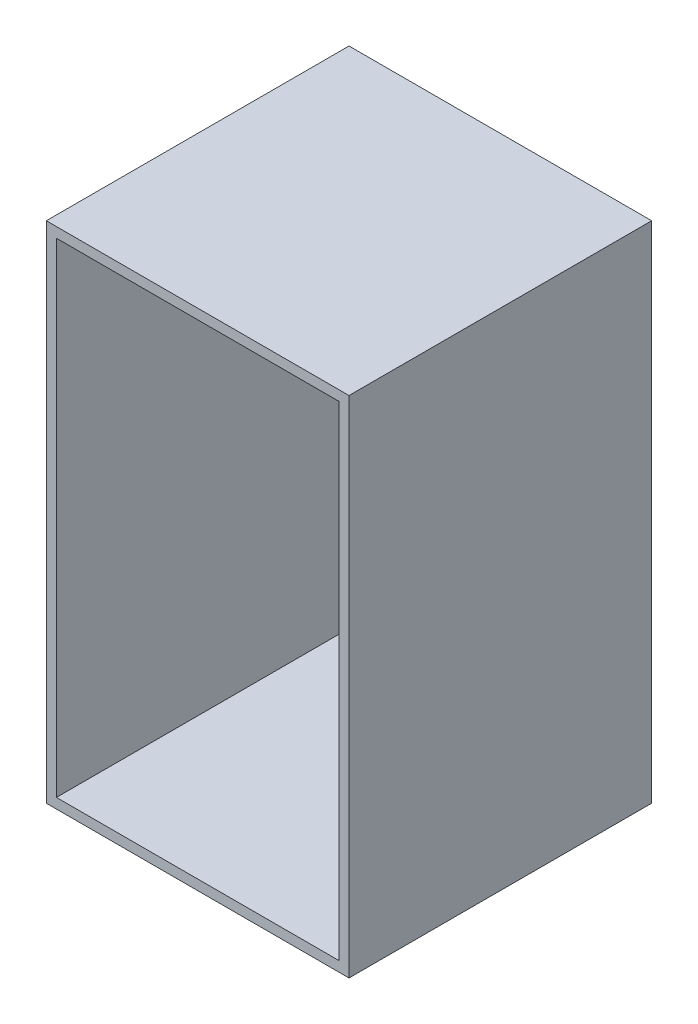
SolidWorks part; units mm, degrees
note: '?' marks a value the reader was unsure of.
ref_plane "Front Plane" through (0, 0, 0) normal (0, 0, 1) x (1, 0, 0)
ref_plane "Top Plane" through (0, 0, 0) normal (0, 1, 0) x (1, 0, 0)
ref_plane "Right Plane" through (0, 0, 0) normal (1, 0, 0) x (0, 0, -1)
sketch "Sketch1" plane through (0, 0, 0) normal (0, 1, 0) x (1, 0, 0)
  line L1 (-38.1, -38.1) -> (38.1, -38.1)
  line L2 (-38.1, -38.1) -> (-38.1, 38.1)
  line L3 (-38.1, 38.1) -> (38.1, 38.1)
  line L4 (38.1, -38.1) -> (38.1, 38.1)
  line L5 (-38.1, -38.1) -> (38.1, 38.1) construction
  line L6 (-38.1, 38.1) -> (38.1, -38.1) construction
  point P0 (0, 0)
  dimension "D1" = 76.2
  dimension "D2" = 76.2
extrude "box" add sketch "Sketch1" along normal blind 127
shell "hollow it" thickness 2.54
sketch "Sketch2" plane through (0, 0, -38.1) normal (0, 0, -1) x (-1, 0, 0)
  line L0 (-38.1, 127) -> (38.1, 127) construction
  line L1 (-29.21, 69.85) -> (-24.892, 69.85)
  line L2 (-29.21, 69.85) -> (-29.21, 6.35)
  line L3 (-29.21, 6.35) -> (-24.892, 6.35)
  line L4 (-24.892, 69.85) -> (-24.892, 6.35)
  line L6 (-38.1, 127) -> (-38.1, 0) construction
  dimension "D1" = 4.318
  dimension "D2" = 63.5
  dimension "D3" = 57.15
  dimension "D4" = 8.89
extrude "slider track" cut sketch "Sketch2" against normal up to surface (2.54 mm away) up to face at (0, 63.5, -35.56)
sketch "Sketch6" plane through (0, 0, -38.1) normal (0, 0, -1) x (-1, 0, 0)
  line L0 (-3.2977, 45.72) -> (-3.2977, 52.07)
  line L1 (-3.2977, 52.07) -> (3.0523, 52.07)
  line L2 (3.0523, 52.07) -> (3.0523, 45.72)
  line L3 (3.0523, 45.72) -> (9.4023, 45.72)
  line L4 (9.4023, 45.72) -> (9.4023, 39.37)
  line L5 (9.4023, 39.37) -> (3.0523, 39.37)
  line L6 (3.0523, 39.37) -> (3.0523, 33.02)
  line L7 (3.0523, 33.02) -> (-3.2977, 33.02)
  line L8 (-3.2977, 33.02) -> (-3.2977, 39.37)
  line L9 (-3.2977, 39.37) -> (-9.6477, 39.37)
  line L10 (-9.6477, 39.37) -> (-9.6477, 45.72)
  line L11 (-9.6477, 45.72) -> (-3.2977, 45.72)
  line L12 (-38.1, 0) -> (38.1, 0) construction
  dimension "D1" = 6.35
  dimension "D2" = 6.35
  dimension "D3" = 6.35
  dimension "D4" = 6.35
  dimension "D5" = 6.35
  dimension "D6" = 6.35
  dimension "D7" = 6.35
  dimension "D8" = 6.35
  dimension "D9" = 6.35
  dimension "D10" = 33.02
extrude "dpad large shape" cut sketch "Sketch6" against normal blind 1.27
sketch "Sketch7" plane through (0, 0, -36.83) normal (0, 0, -1) x (-1, 0, 0)
  line L0 (-3.2977, 45.72) -> (-9.6477, 45.72) construction
  line L1 (-9.6477, 45.72) -> (-9.6477, 39.37) construction
  line L2 (3.0523, 33.02) -> (3.0523, 39.37) construction
  line L3 (-3.2977, 33.02) -> (3.0523, 33.02) construction
  line L4 (3.0523, 39.37) -> (9.4023, 39.37) construction
  line L5 (9.4023, 39.37) -> (9.4023, 45.72) construction
  line L6 (3.0523, 45.72) -> (3.0523, 52.07) construction
  line L7 (-3.2977, 52.07) -> (-3.2977, 45.72) construction
  line L8 (3.0523, 52.07) -> (-3.2977, 52.07) construction
  circle A0 centre (-0.1227, 48.895) radius 1.905
  circle A1 centre (6.2273, 42.672) radius 1.905
  circle A2 centre (-0.1227, 36.195) radius 1.905
  circle A3 centre (-6.4727, 42.545) radius 1.905
  point P12 (3.0523, 36.195)
  point P17 (6.2273, 39.37)
  dimension "D3" = 3.81
  dimension "D6" = 3.81
  dimension "D9" = 3.81
  dimension "D13" = 3.81
  dimension "D1" = 3.175
  dimension "D2" = 3.175
  dimension "D4" = 3.175
  dimension "D5" = 3.175
  dimension "D7" = 3.302
  dimension "D8" = 3.175
  dimension "D10" = 3.175
  dimension "D11" = 3.175
  dimension "D12" = 3.175
extrude "dpad tiny holes" cut sketch "Sketch7" against normal blind 1.27
sketch "Sketch8" plane through (0, 0, -38.1) normal (0, 0, -1) x (-1, 0, 0)
  line L0 (38.1, 127) -> (38.1, 0) construction
  line L1 (-38.1, 127) -> (38.1, 127) construction
  circle A0 centre (20.32, 19.05) radius 12.7
  dimension "D1" = 25.4
  dimension "D2" = 17.78
  dimension "D3" = 107.95
extrude "dial large ring" cut sketch "Sketch8" against normal blind 1.27
ref_point "dial center"
sketch "Sketch9" plane through (0, 0, -36.83) normal (0, 0, -1) x (-1, 0, 0)
  circle A0 centre (20.32, 19.05) radius 5.08
  dimension "D1" = 10.16
extrude "dial small hole" cut sketch "Sketch9" against normal blind 1.27
sketch "Sketch12" plane through (0, 0, -38.1) normal (0, 0, -1) x (-1, 0, 0)
  line L0 (38.1, 127) -> (38.1, 0) construction
  line L1 (-11.43, 30.48) -> (-2.54, 30.48)
  line L2 (-11.43, 30.48) -> (-11.43, 5.08)
  line L3 (-11.43, 5.08) -> (-2.54, 5.08)
  line L4 (-2.54, 30.48) -> (-2.54, 5.08)
  line L5 (-38.1, 0) -> (38.1, 0) construction
  dimension "D1" = 25.4
  dimension "D2" = 8.89
  dimension "D3" = 40.64
  dimension "D4" = 5.08
extrude "hole for scroll wheel" cut sketch "Sketch12" against normal blind 2.54
sketch "Sketch14" plane through (2.54, 0, 0) normal (1, 0, 0) x (0, 0, -1)
  line L0 (38.1, 5.08) -> (38.1, 30.48) construction
  circle A0 centre (38.1, 17.78) radius 6.35
extrude "nibble base 1" add sketch "Sketch14" against normal blind 5.08
sketch "Sketch15" plane through (11.43, 0, 0) normal (-1, 0, 0) x (0, 0, 1)
  line L0 (-38.1, 30.48) -> (-38.1, 5.08) construction
  circle A0 centre (-38.1, 17.78) radius 6.35
extrude "nibble base 2" add sketch "Sketch15" against normal blind 5.08
sketch "Sketch16" plane through (11.43, 0, 0) normal (-1, 0, 0) x (0, 0, 1)
  circle A0 centre (-38.1, 17.78) radius 3.302
extrude "nibble holes" cut sketch "Sketch16" against normal up to surface and the other way up to surface up to face at (16.51, 17.78, -41.275) other way up to face at (-2.54, 17.78, -41.275)
sketch "Sketch17" plane through (0, 0, -38.1) normal (0, 0, -1) x (-1, 0, 0)
  line L0 (31.75, 65.405) -> (31.75, 61.595) construction
  line L1 (33.782, 65.405) -> (33.782, 61.595)
  line L2 (29.718, 65.405) -> (29.718, 61.595)
  line L3 (-38.1, 0) -> (38.1, 0) construction
  line L4 (38.1, 127) -> (38.1, 0) construction
  arc A0 (33.782, 65.405) -> (29.718, 65.405) centre (31.75, 65.405) ccw
  arc A1 (29.718, 61.595) -> (33.782, 61.595) centre (31.75, 61.595) ccw
  point P2 (31.75, 63.5)
  point P11 (25.4, 63.5)
  dimension "D1" = 2.032
  dimension "D2" = 3.81
  dimension "D3" = 63.5
  dimension "D4" = 6.35
  dimension "D5" = 6.35
ref_axis "axis of button" through (-25.4, 63.5, -38.1) along (0, 0, -1)?
extrude "single button leg hole" cut sketch "Sketch17" against normal blind 2.54
pattern_circular "moar leg holes" count 4 over 360 about axis through (-25.4, 63.5, 0) along (0, 0, 1) of "single button leg hole"
sketch "Sketch19" plane through (0, 0, -38.1) normal (0, 0, -1) x (-1, 0, 0)
  line L0 (-38.1, 0) -> (38.1, 0) construction
  line L1 (-22.86, 121.4316) -> (22.86, 121.4316)
  line L2 (-22.86, 121.4316) -> (-22.86, 75.7116)
  line L3 (-22.86, 75.7116) -> (22.86, 75.7116)
  line L4 (22.86, 121.4316) -> (22.86, 75.7116)
  line L5 (-22.86, 121.4316) -> (22.86, 75.7116) construction
  line L6 (-22.86, 75.7116) -> (22.86, 121.4316) construction
  point P0 (0, 98.5716)
  point P5 (0, 0)
  dimension "D1" = 45.72
  dimension "D2" = 45.72
  dimension "D3" = 0
extrude "base for joystick" add sketch "Sketch19" along normal blind 3.81 and the other way blind 15.24
ref_point "joystick center"
sketch "Sketch21" plane through (0, 0, -41.91) normal (0, 0, -1) x (-1, 0, 0)
  line L1 (20.32, 78.2516) -> (-20.32, 78.2516)
  line L2 (20.32, 78.2516) -> (20.32, 118.8916)
  line L3 (20.32, 118.8916) -> (-20.32, 118.8916)
  line L4 (-20.32, 78.2516) -> (-20.32, 118.8916)
  line L5 (20.32, 78.2516) -> (-20.32, 118.8916) construction
  line L6 (20.32, 118.8916) -> (-20.32, 78.2516) construction
  point P0 (0, 98.5716)
  dimension "D1" = 2.54
  dimension "D2" = 2.54
extrude "joystick hole" cut sketch "Sketch21" against normal through all
ref_point "joystick small nibbles"
ref_point "joystick large nibbles"
sketch "Sketch22" plane through (-20.32, 0, 0) normal (1, 0, 0) x (0, 0, -1)
  circle A0 centre (32.385, 98.5716) radius 3.175
  dimension "D1" = 6.35
extrude "large nibbles" cut sketch "Sketch22" against normal up to surface and the other way up to surface up to face at (-22.86, 98.5716, -40.005) other way up to face at (22.86, 98.5716, -40.005)
sketch "Sketch23" plane through (0, 118.8916, 0) normal (0, -1, 0) x (1, 0, 0)
  circle A0 centre (0, -32.385) radius 4.445
  dimension "D1" = 8.89
extrude "small nibbles" cut sketch "Sketch23" against normal up to surface and the other way offset from surface (48.26 mm away) 5.08 up to face at (0, 124.46, 1.27) other way up to face at (0, 75.7116, -29.21)
